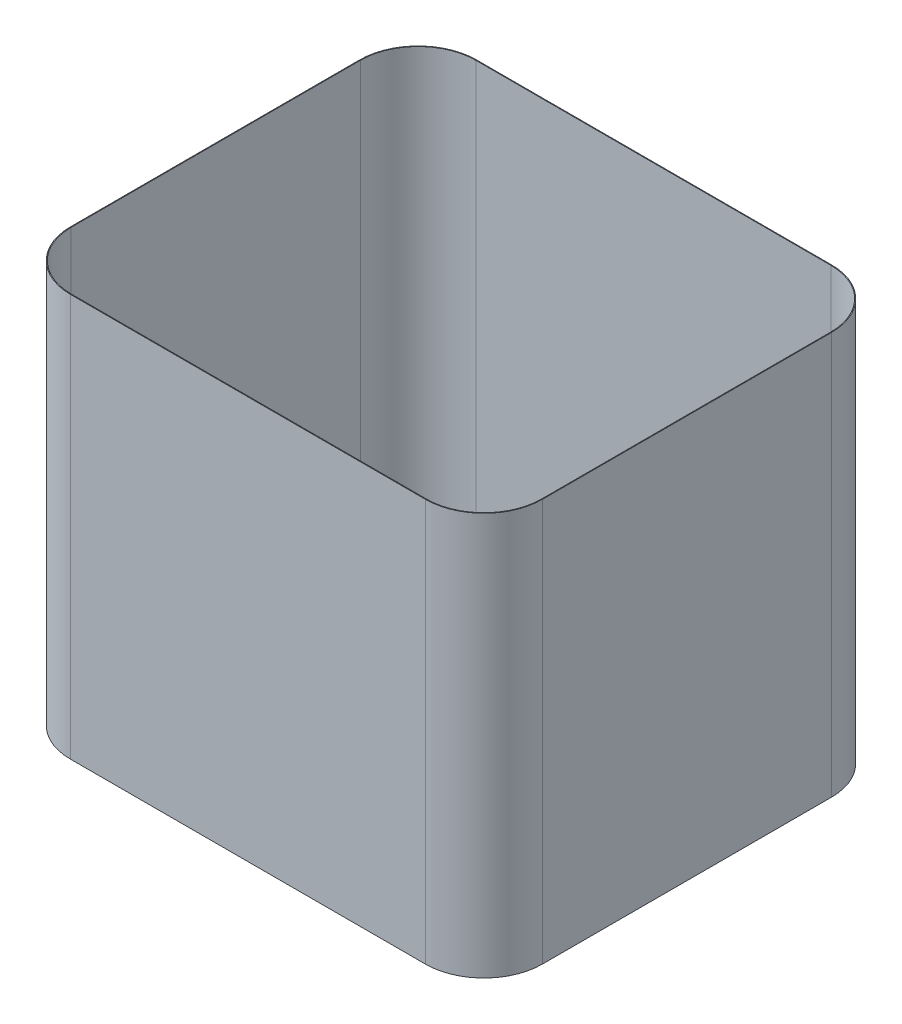
SolidWorks part; units mm, degrees
ref_plane "Front" through (0, 0, 0) normal (0, 0, 1) x (1, 0, 0)
ref_plane "Top" through (0, 0, 0) normal (0, 1, 0) x (1, 0, 0)
ref_plane "Right" through (0, 0, 0) normal (1, 0, 0) x (0, 0, -1)
sketch "Sketch1" plane through (0, 0, 0) normal (0, 1, 0) x (1, 0, 0)
  line L0 (-203.2, -406.4) -> (1028.7, -406.4)
  line L1 (0, 0) -> (825.5, 0) construction
  line L2 (0, 0) -> (0, 596.9) construction
  line L3 (0, 596.9) -> (825.5, 596.9) construction
  line L4 (825.5, 0) -> (825.5, 596.9) construction
  line L5 (0, 0) -> (825.5, 596.9) construction
  line L6 (0, 596.9) -> (825.5, 0) construction
  line L7 (1231.9, -203.2) -> (1231.9, 800.1)
  line L8 (-203.2, 1003.3) -> (1028.7, 1003.3)
  line L9 (-406.4, -203.2) -> (-406.4, 800.1)
  line L10 (-406.4, -406.4) -> (1231.9, -406.4) construction
  line L11 (-406.4, -406.4) -> (-406.4, 1003.3) construction
  line L12 (1231.9, -406.4) -> (1231.9, 1003.3) construction
  line L13 (-406.4, 1003.3) -> (1231.9, 1003.3) construction
  arc A0 (-203.2, -406.4) -> (-406.4, -203.2) centre (-203.2, -203.2) cw
  arc A1 (1028.7, -406.4) -> (1231.9, -203.2) centre (1028.7, -203.2) ccw
  arc A2 (1231.9, 800.1) -> (1028.7, 1003.3) centre (1028.7, 800.1) ccw
  arc A3 (-203.2, 1003.3) -> (-406.4, 800.1) centre (-203.2, 800.1) ccw
  point P4 (412.75, 298.45)
  dimension "D4" = 203.2
  dimension "D1" = 596.9
  dimension "D2" = 825.5
  dimension "D3" = 406.4
extrude "Boss-Extrude1" add sketch "Sketch1" along normal blind 1397
shell "Shell1" thickness 2.54 removed face at (412.75, 0, -298.45)
sketch "Sketch3" plane through (0, 1394.46, 0) normal (0, -1, 0) x (1, 0, 0)
  line L4 (-403.86, 203.2) -> (-403.86, -800.1)
  line L5 (-203.2, -1000.76) -> (1028.7, -1000.76)
  line L6 (1229.36, -800.1) -> (1229.36, 203.2)
  line L7 (1028.7, 403.86) -> (-203.2, 403.86)
  line L8 (-403.86, 203.2) -> (-403.86, -800.1)
  line L9 (-203.2, -1000.76) -> (1028.7, -1000.76)
  line L10 (1229.36, -800.1) -> (1229.36, 203.2)
  line L11 (1028.7, 403.86) -> (-203.2, 403.86)
  arc A4 (-203.2, 403.86) -> (-403.86, 203.2) centre (-203.2, 203.2) ccw
  arc A5 (-403.86, -800.1) -> (-203.2, -1000.76) centre (-203.2, -800.1) ccw
  arc A6 (1028.7, -1000.76) -> (1229.36, -800.1) centre (1028.7, -800.1) ccw
  arc A7 (1229.36, 203.2) -> (1028.7, 403.86) centre (1028.7, 203.2) ccw
  arc A8 (-203.2, 403.86) -> (-403.86, 203.2) centre (-203.2, 203.2) ccw
  arc A9 (-403.86, -800.1) -> (-203.2, -1000.76) centre (-203.2, -800.1) ccw
  arc A10 (1028.7, -1000.76) -> (1229.36, -800.1) centre (1028.7, -800.1) ccw
  arc A11 (1229.36, 203.2) -> (1028.7, 403.86) centre (1028.7, 203.2) ccw
  dimension "D1" = 0
extrude "Cut-Extrude3" cut sketch "Sketch3" against normal up to next
